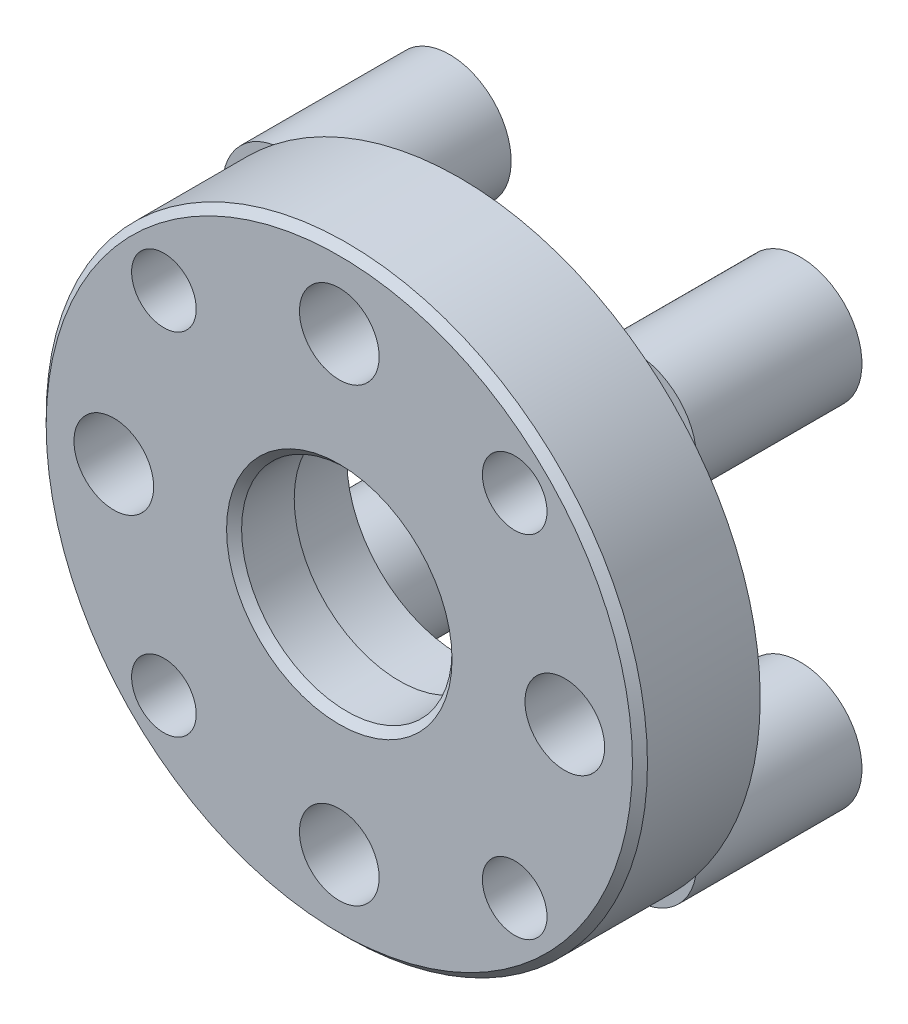
SolidWorks part; units mm, degrees
material "ABS"
ref_plane "Front Plane" through (0, 0, 0) normal (0, 0, 1) x (1, 0, 0)
ref_plane "Top Plane" through (0, 0, 0) normal (0, 1, 0) x (1, 0, 0)
ref_plane "Right Plane" through (0, 0, 0) normal (1, 0, 0) x (0, 0, -1)
ref_plane "Output Plane" through (0, 0, 25.2347) normal (0, 0, -1) x (-1, 0, 0)
sketch "CYC Output Sketch" plane through (0, 0, 25.2347) normal (0, 0, 1) x (1, 0, 0)
  line L1 (11.6673, 11.6673) -> (-11.6673, 11.6673) construction
  line L2 (-11.6673, 11.6673) -> (-11.6673, -11.6673) construction
  line L3 (-11.6673, -11.6673) -> (11.6673, -11.6673) construction
  line L4 (11.6673, -11.6673) -> (11.6673, 11.6673) construction
  circle A0 centre (0, 0) radius 16.5 construction
sketch "Sketch3" plane through (0, 0, 25.2347) normal (0, 0, -1) x (-1, 0, 0)
  circle A0 centre (-11.6673, 11.6673) radius 4
  circle A1 centre (11.6673, 11.6673) radius 4
  circle A2 centre (11.6673, -11.6673) radius 4
  circle A3 centre (-11.6673, -11.6673) radius 4
  dimension "D1" = 8
extrude "Boss-Extrude1" add sketch "Sketch3" along normal blind 11
sketch "Sketch6" plane through (0, 0, 25.2347) normal (0, 0, 1) x (1, 0, 0)
  arc A0 (10.6823, 16.9082) -> (-16.9082, 10.6823) centre (0, 0) ccw
  arc A18 (16.9082, -10.6823) -> (10.6823, 16.9082) centre (0, 0) ccw
  arc A19 (-10.6823, -16.9082) -> (16.9082, -10.6823) centre (0, 0) ccw
  arc A20 (-16.9082, 10.6823) -> (-10.6823, -16.9082) centre (0, 0) ccw
  circle A23 centre (0, 0) radius 7.5
  dimension "D2" = 40
  dimension "D1" = 15
extrude "Boss-Extrude6" add sketch "Sketch6" along normal blind 8 contours A23 | A0 A20 A19 A18 region at (0, 0, 25.2347)
sketch "Sketch8" plane through (0, 0, 33.2347) normal (0, 0, 1) x (1, 0, 0)
  line L0 (0, 0) -> (11.6673, 11.6673) construction
  line L1 (0, 0) -> (16.5, 0) construction
  circle A0 centre (0, 0) radius 16.5 construction
  circle A1 centre (11.6673, 11.6673) radius 1.6
  circle A2 centre (11.6673, -11.6673) radius 1.6
  circle A3 centre (-11.6673, -11.6673) radius 1.6
  circle A4 centre (-11.6673, 11.6673) radius 1.6
  point P16 (0, 0)
  dimension "D1" = 33
  dimension "D2" = 45
  dimension "D3" = 3.2
  dimension "D4" = 4
extrude "Cut-Extrude1" cut sketch "Sketch8" against normal through all
sketch "Sketch9" plane through (0, 0, 14.2347) normal (0, 0, 1) x (1, 0, 0)
  circle A0 centre (11.6673, 11.6673) radius 3
  circle A1 centre (11.6673, -11.6673) radius 3
  circle A2 centre (-11.6673, -11.6673) radius 3
  circle A3 centre (-11.6673, 11.6673) radius 3
  point P12 (0, 0)
  dimension "D1" = 6
  dimension "D2" = 4
extrude "Cut-Extrude2" cut sketch "Sketch9" along normal blind 3 from surface starting at face at (13.2673, 11.6673, 14.2347)
sketch "Sketch10" plane through (0, 0, 14.2347) normal (0, 0, -1) x (-1, 0, 0)
  circle A0 centre (11.6673, 11.6673) radius 4.1
  circle A1 centre (11.6673, 11.6673) radius 4
  circle A2 centre (11.6673, -11.6673) radius 4
  circle A3 centre (11.6673, -11.6673) radius 4.1
  circle A4 centre (-11.6673, -11.6673) radius 4
  circle A5 centre (-11.6673, -11.6673) radius 4.1
  circle A6 centre (-11.6673, 11.6673) radius 4
  circle A7 centre (-11.6673, 11.6673) radius 4.1
  point P16 (0, 0)
  dimension "D1" = 8
  dimension "D2" = 8.2
  dimension "D3" = 4
extrude "Boss-Extrude8" add sketch "Sketch10" against normal blind 11
sketch "Sketch11" plane through (0, 0, 33.2347) normal (0, 0, 1) x (1, 0, 0)
  line L0 (0, 0) -> (0, 15) construction
  circle A0 centre (0, 15) radius 2.65
  circle A1 centre (15, 0) radius 2.65
  circle A2 centre (0, -15) radius 2.65
  circle A3 centre (-15, 0) radius 2.65
  circle A4 centre (-11.6673, 11.6673) radius 2.15
  circle A5 centre (11.6673, 11.6673) radius 2.15
  circle A6 centre (11.6673, -11.6673) radius 2.15
  circle A7 centre (-11.6673, -11.6673) radius 2.15
  point P13 (0, 0)
  dimension "D2" = 5.3
  dimension "D4" = 4.3
  dimension "D1" = 15
  dimension "D3" = 4
extrude "Cut-Extrude3" cut sketch "Sketch11" against normal blind 8
sketch "Sketch12" plane through (0, 0, 33.2347) normal (0, 0, 1) x (1, 0, 0)
  circle A0 centre (0, 0) radius 7.5
  circle A1 centre (0, 0) radius 7
  dimension "D1" = 15
  dimension "D2" = 14
extrude "Boss-Extrude9" add sketch "Sketch12" against normal blind 4
chamfer "Chamfer1" distance 0.5 angle 45 2 edges at (7, 0, 33.2347) (20, 0, 33.2347)
equation "\"RingPinShaft\"= 5.05"
equation "\"CenterBearingOut\"=32.00"
equation "\"RingPostIn\"=5.15"
equation "\"CamBearingOut\"=15.1"
equation "\"DiskOutputShaft\"=10.1"
equation "\"CenterShaft\"=25.2"
equation "\"Eccentricity\"=2"
equation "\"CycCamShaft\"=10.05"
equation "\"D2@Sketch6\"=\"OutputBearing\""
equation "\"OutputBearing\"=40"
